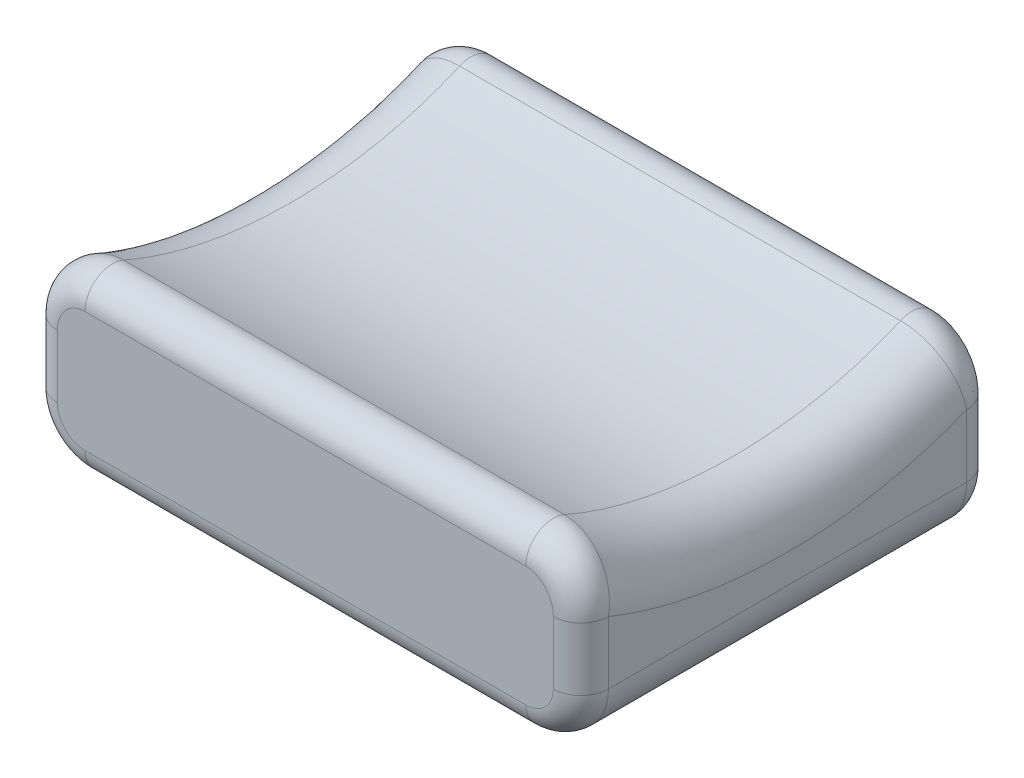
SolidWorks part; units mm, degrees
ref_plane "Front Plane" through (0, 0, 0) normal (0, 0, 1) x (1, 0, 0)
ref_plane "Top Plane" through (0, 0, 0) normal (0, 1, 0) x (1, 0, 0)
ref_plane "Right Plane" through (0, 0, 0) normal (1, 0, 0) x (0, 0, -1)
sketch "Sketch1" plane through (0, 0, 0) normal (1, 0, 0) x (0, 0, -1)
  line L1 (-3.75, -1.75) -> (3.75, -1.75)
  line L2 (-3.75, -1.75) -> (-3.75, 1.75)
  line L4 (3.75, -1.75) -> (3.75, 1.75)
  line L5 (-3.75, -1.75) -> (3.75, 1.75) construction
  line L6 (-3.75, 1.75) -> (3.75, -1.75) construction
  spline S0 degree 3 poles (-3.75, 1.75) (-2.6252, 1.0823) (0, 0.4656) (2.6252, 1.0823) (3.75, 1.75) knots 0 0 0 0 0.5 1 1 1 1
  point P0 (0, 0)
  dimension "D1" = 7.5
  dimension "D2" = 3.5
extrude "Boss-Extrude1" add sketch "Sketch1" along normal blind 10
fillet "Fillet1" radius 1 1 edges at (10, -1.75, 0)
fillet "Fillet2" radius 1 1 edges
fillet "Fillet3" radius 1 1 edges
fillet "Fillet4" radius 1 1 edges at (0, -1.75, 0)
fillet "Fillet5" radius 0.5 8 edges at (9.7256, 1.3903, 3.75) (10, -0.0682, 3.75) (9.7071, -1.4571, 3.75) (5, -1.75, 3.75) (0.2929, -1.4571, 3.75) (0, -0.0682, 3.75) (0.4377, 1.5497, 3.75) (5, 1.75, 3.75)
fillet "Fillet6" radius 0.5 8 edges at (9.5623, 1.5497, -3.75) (10, -0.0682, -3.75) (9.7071, -1.4571, -3.75) (5, -1.75, -3.75) (0.2929, -1.4571, -3.75) (0, -0.0682, -3.75) (0.2744, 1.3903, -3.75) (5, 1.75, -3.75)
